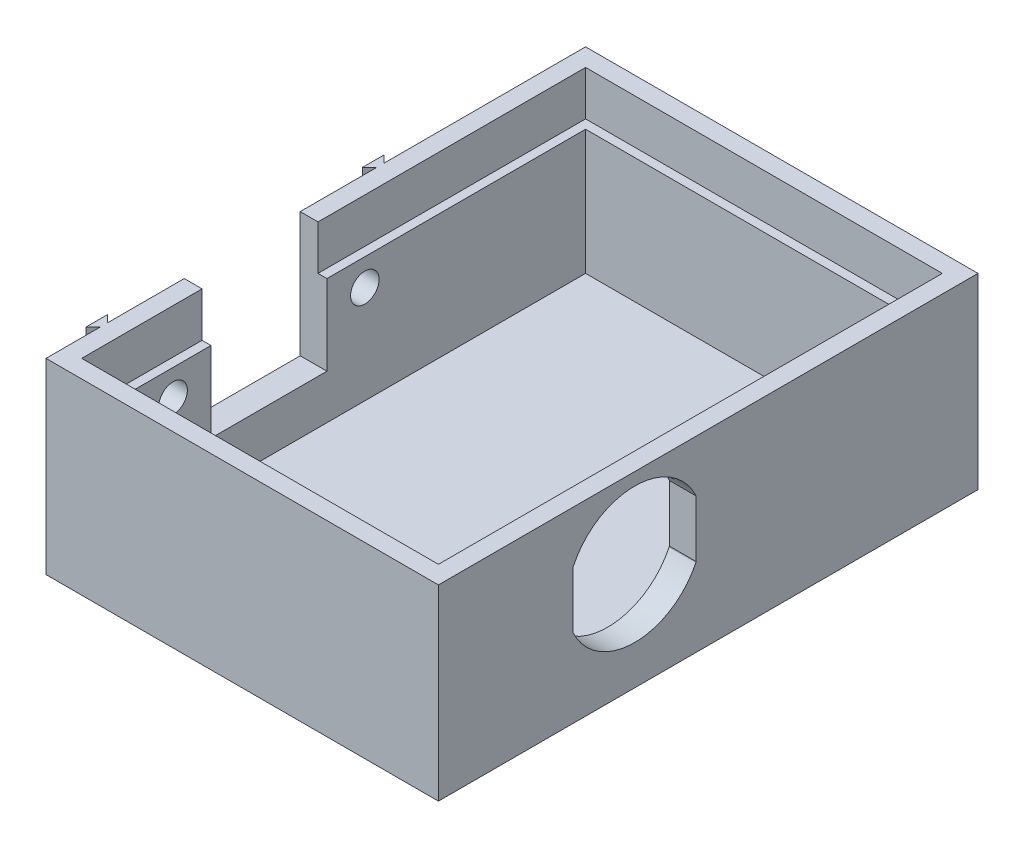
SolidWorks part; units mm, degrees
ref_plane "Alzado" through (0, 0, 0) normal (0, 0, 1) x (1, 0, 0)
ref_plane "Planta" through (0, 0, 0) normal (0, 1, 0) x (1, 0, 0)
ref_plane "Vista lateral" through (0, 0, 0) normal (1, 0, 0) x (0, 0, -1)
sketch "Croquis3" plane through (0, 0, 0) normal (0, 1, 0) x (1, 0, 0)
  line L0 (-22, 46.7304) -> (-132, 46.7304) construction
  line L1 (-22, -13.7696) -> (22, -13.7696)
  line L2 (-22, -13.7696) -> (-22, 46.7304)
  line L3 (-22, 46.7304) -> (22, 46.7304)
  line L4 (22, -13.7696) -> (22, 46.7304)
  line L5 (-22, -13.7696) -> (22, 46.7304) construction
  line L6 (-22, 46.7304) -> (22, -13.7696) construction
  line L7 (0, 0) -> (0, 16.4804) construction
  point P0 (0, 16.4804)
  dimension "D1" = 60.5
  dimension "D2" = 44
extrude "Saliente-Extruir1" add sketch "Croquis3" along normal blind 2
sketch "Croquis4" plane through (0, 2, 0) normal (0, 1, 0) x (1, 0, 0)
  line L0 (22, -13.7696) -> (22, 46.7304) construction
  line L1 (-22, -13.7696) -> (22, -13.7696)
  line L2 (-22, -13.7696) -> (-22, 1.7304)
  line L3 (-22, 46.7304) -> (22, 46.7304)
  line L4 (22, -13.7696) -> (22, 46.7304)
  line L5 (-22, -13.7696) -> (22, 46.7304) construction
  line L6 (-22, 46.7304) -> (22, -13.7696) construction
  line L7 (-22, 8.2304) -> (-19, 8.2304) construction
  line L8 (-19, -10.7696) -> (19, -10.7696)
  line L9 (-19, -10.7696) -> (-19, 1.7304)
  line L10 (-19, 43.7304) -> (19, 43.7304)
  line L11 (19, -10.7696) -> (19, 43.7304)
  line L12 (-19, -10.7696) -> (19, 43.7304) construction
  line L13 (-19, 43.7304) -> (19, -10.7696) construction
  line L14 (-22, 14.7304) -> (-19, 14.7304)
  line L15 (-22, 1.7304) -> (-19, 1.7304)
  line L16 (-22, 14.7304) -> (-22, 46.7304)
  line L17 (-19, 14.7304) -> (-19, 43.7304)
  line L18 (22, 46.7304) -> (-22, 46.7304) construction
  line L19 (-22, -13.7696) -> (22, -13.7696) construction
  line L20 (-22, 46.7304) -> (-22, -13.7696) construction
  point P0 (0, 16.4804)
  point P8 (0, 16.4804)
  dimension "D1" = 3
  dimension "D2" = 3
  dimension "D3" = 13
  dimension "D4" = 15.5
extrude "Saliente-Extruir2" add sketch "Croquis4" along normal blind 19
sketch "Croquis5" plane through (0, 2, 0) normal (0, 1, 0) x (1, 0, 0)
  line L1 (-19, 14.7304) -> (-22, 14.7304)
  line L2 (-19, 14.7304) -> (-19, 1.7304)
  line L3 (-19, 1.7304) -> (-22, 1.7304)
  line L4 (-22, 14.7304) -> (-22, 1.7304)
extrude "Saliente-Extruir3" add sketch "Croquis5" along normal blind 5
sketch "Croquis6" plane through (0, 21, 0) normal (0, 1, 0) x (1, 0, 0)
  line L8 (-20, -11.7696) -> (-20, 44.7304)
  line L9 (-19, -10.7696) -> (19, -10.7696)
  line L10 (-19, -10.7696) -> (-19, 43.7304)
  line L11 (-19, 43.7304) -> (19, 43.7304)
  line L12 (19, -10.7696) -> (19, 43.7304)
  line L13 (-20, 44.7304) -> (20, 44.7304)
  line L14 (20, -11.7696) -> (20, 44.7304)
  line L15 (-20, -11.7696) -> (20, -11.7696)
  dimension "D1" = 1
extrude "Cortar-Extruir1" cut sketch "Croquis6" against normal blind 5
sketch "Croquis7" plane through (0, 21, 0) normal (0, 1, 0) x (1, 0, 0)
  line L0 (-22, -7.2696) -> (-19, -7.2696) construction
  line L1 (-22, 1.7304) -> (-22, -13.7696) construction
  line L2 (-19, -10.7696) -> (-19, 43.7304) construction
  line L3 (-22, 1.7304) -> (-19, 1.7304) construction
  line L4 (-22, -7.2696) -> (-22, -6.8696)
  line L5 (-22, -6.8696) -> (-22.8, -6.0696)
  line L6 (-22.8, -6.0696) -> (-22.8, -8.4696)
  line L7 (-22.8, -8.4696) -> (-22, -7.6696)
  line L8 (-22, -7.6696) -> (-22, -7.2696)
  line L9 (-19, 8.2304) -> (-22, 8.2304) construction
  line L10 (-19, 1.7304) -> (-19, 14.7304) construction
  line L11 (-22, 14.7304) -> (-22, 1.7304) construction
  line L12 (-22, 24.1304) -> (-22, 23.7304)
  line L13 (-22.8, 24.9304) -> (-22, 24.1304)
  line L14 (-22.8, 22.5304) -> (-22.8, 24.9304)
  line L15 (-22, 23.3304) -> (-22.8, 22.5304)
  line L16 (-22, 23.7304) -> (-22, 23.3304)
  point P12 (-22, -7.4696)
  dimension "D1" = 9
  dimension "D2" = 0.4
  dimension "D3" = 0.4
  dimension "D4" = 45
  dimension "D5" = 45
  dimension "D6" = 0.8
extrude "Saliente-Extruir4" add sketch "Croquis7" against normal blind 15
fillet "Redondeo1" radius 2 2 edges at (-22, 6, 7.2696) (-22, 6, -23.7304)
sketch "Croquis8" plane through (22, 0, 0) normal (1, 0, 0) x (0, 0, -1)
  line L0 (8.2304, 21) -> (8.2304, 3) construction
  line L1 (-13.7696, 21) -> (-13.7696, 0) construction
  line L2 (15.0979, 8.7446) -> (15.1304, 8.8141)
  line L3 (15.1304, 8.8141) -> (15.1304, 15.1859)
  line L4 (8.2304, 12) -> (15.1304, 12) construction
  line L5 (1.3304, 8.8141) -> (1.3304, 15.1859)
  line L6 (24.64, 0) -> (-24.64, 0) construction
  line L8 (-13.7696, 21) -> (46.7304, 21) construction
  arc A0 (1.3304, 8.8141) -> (15.0979, 8.7446) centre (8.2304, 12) ccw
  arc A1 (15.1304, 15.1859) -> (1.3304, 15.1859) centre (8.2304, 12) ccw
  dimension "D1" = 15.2
  dimension "D2" = 13.8
  dimension "D3" = 3
  dimension "D4" = 22
  dimension "D5" = 0.0767
extrude "Cortar-Extruir4" cut sketch "Croquis8" against normal blind 10 contours L3 A1 L5 A0 region at (22, 12, -8.2304)
sketch "Croquis9" plane through (-22, 0, 0) normal (-1, 0, 0) x (0, 0, 1)
  line L0 (-23.3304, 21) -> (-14.7304, 21) construction
  line L1 (-8.2304, 21) -> (-8.2304, 7) construction
  line L3 (-14.7304, 7) -> (-1.7304, 7) construction
  circle A0 centre (-18.9804, 13) radius 1.6
  circle A1 centre (2.5196, 13) radius 1.6
  dimension "D1" = 3.2
  dimension "D2" = 8
  dimension "D3" = 10.75
  dimension "D4" = 10.75
extrude "Cortar-Extruir5" cut sketch "Croquis9" against normal blind 10
sketch "Croquis10" plane through (-22, 0, 0) normal (-1, 0, 0) x (0, 0, 1)
  line L0 (-1.7304, 7) -> (-1.7304, 0) construction
  line L1 (-46.7304, 0) -> (13.7696, 0) construction
